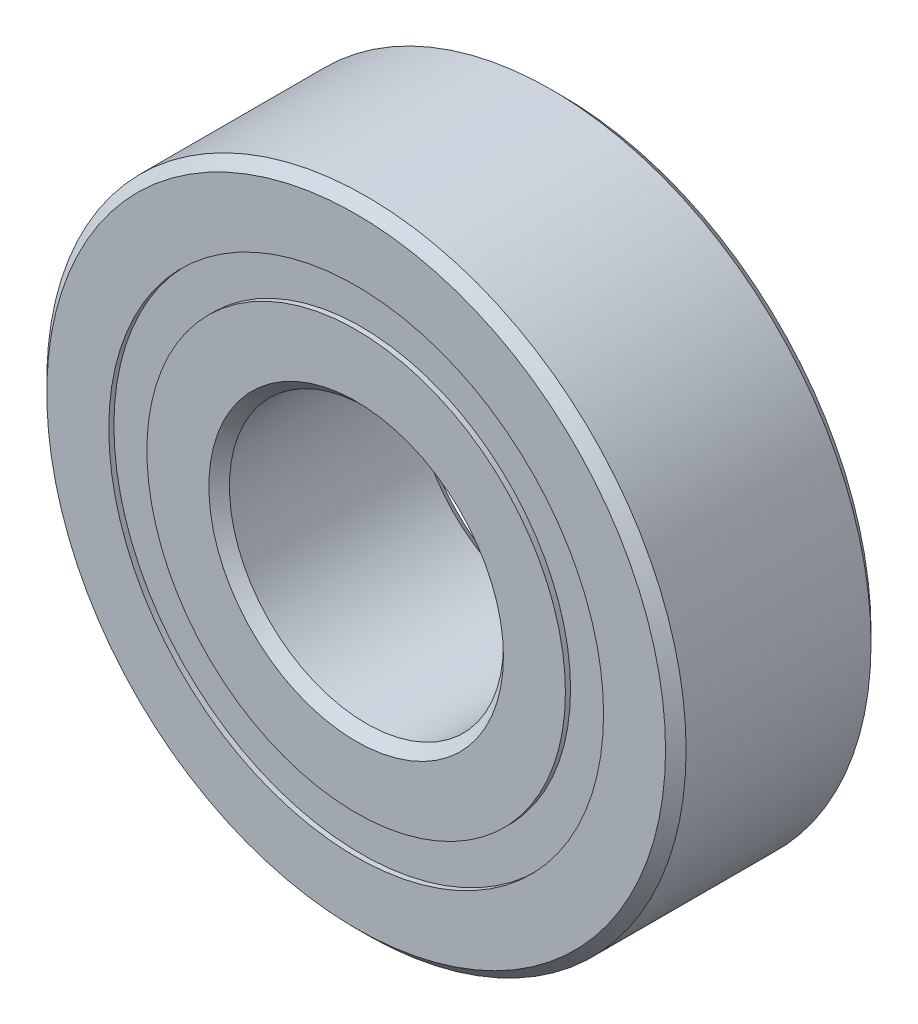
SolidWorks part; units mm, degrees
note: '?' marks a value the reader was unsure of.
ref_plane "Front Plane" through (0, 0, 0) normal (0, 0, 1) x (1, 0, 0)
ref_plane "Top Plane" through (0, 0, 0) normal (0, 1, 0) x (1, 0, 0)
ref_plane "Right Plane" through (0, 0, 0) normal (1, 0, 0) x (0, 0, -1)
sketch "Sketch1" plane through (0, 0, 0) normal (1, 0, 0) x (0, 0, -1)
  line L0 (-3.5719, 0) -> (3.5719, 0) construction
  line L1 (0, 11.1125) -> (0, -11.1125) construction
  line L2 (3.2147, 11.1125) -> (-3.2147, 11.1125)
  line L3 (-3.2147, 11.1125) -> (-3.5719, 10.7553)
  line L4 (-3.5719, 10.7553) -> (-3.5719, 8.6004)
  line L5 (-3.5719, 8.6004) -> (-1.5875, 8.6004)
  line L6 (3.5719, 8.6004) -> (1.5875, 8.6004)
  line L7 (3.5719, 10.7553) -> (3.5719, 8.6004)
  line L8 (3.2147, 11.1125) -> (3.5719, 10.7553)
  line L9 (0, 11.1125) -> (0, 7.9375) construction
  line L10 (0, 7.9375) -> (0, 4.7625) construction
  arc A0 (-1.5875, 8.6004) -> (1.5875, 8.6004) centre (0, 7.9375) cw
  point P14 (0, 4.7625)
  dimension "Width" = 7.1437
  dimension "OD" = 22.225
  dimension "D1" = 45
  dimension "D2" = 0.3572
  dimension "Shaft Dia" = 9.525
  dimension "D3" = 3.175
  dimension "D4" = 0.6629
revolve "Revolve1" add sketch "Sketch1" angle 360 about L0
sketch "Sketch3" plane through (0, 0, 0) normal (1, 0, 0) x (0, 0, -1)
  line L0 (-3.5719, 7.2746) -> (-1.5875, 7.2746)
  line L1 (0, 11.1125) -> (0, -11.1125) construction
  line L2 (-3.5719, 10.7553) -> (-3.5719, 8.6004) construction
  line L3 (-3.5719, 7.2746) -> (-3.5719, 5.1197)
  line L4 (-3.2147, 11.1125) -> (-3.5719, 10.7553) construction
  line L5 (-3.5719, 5.1197) -> (-3.2147, 4.7625)
  line L6 (-3.2147, 4.7625) -> (3.2147, 4.7625)
  line L7 (3.2147, 11.1125) -> (3.2147, -11.1125) construction
  line L8 (3.2147, 4.7625) -> (3.5719, 5.1197)
  line L9 (3.5719, -10.7553) -> (3.5719, 10.7553) construction
  line L10 (3.5719, 5.1197) -> (3.5719, 7.2746)
  line L11 (3.5719, 7.2746) -> (1.5875, 7.2746)
  line L13 (3.2147, 11.1125) -> (3.5719, 10.7553) construction
  arc A0 (1.5875, 8.6004) -> (-1.5875, 8.6004) centre (0, 7.9375) ccw construction
  arc A1 (1.5875, 7.2746) -> (-1.5875, 7.2746) centre (0, 7.9375) cw
revolve "Revolve3" add sketch "Sketch3" angle 360 about L0
sketch "Sketch4" plane through (0, 0, 0) normal (1, 0, 0) x (0, 0, -1)
  line L0 (-1.7204, 7.9375) -> (1.7204, 7.9375)
  arc A2 (-1.7204, 7.9375) -> (1.7204, 7.9375) centre (0, 7.9375) cw
  arc A3 (1.5875, 8.6004) -> (-1.5875, 8.6004) centre (0, 7.9375) ccw construction
revolve "Revolve4" add sketch "Sketch4" angle 360 about L0
ref_axis "Axis1" through (0, 0, -3.5719) along (0, 0, 1)?
pattern_circular "CirPattern1" count 10 every 36 about axis through (0, 0, 0) along (0, 0, 1) of bodies 104
sketch "Sketch5" plane through (0, 0, 0) normal (1, 0, 0) x (0, 0, -1)
  line L0 (-3.5719, 8.6004) -> (-1.5875, 8.6004) construction
  line L1 (-3.3933, 8.6004) -> (-1.7204, 8.6004)
  line L2 (-3.3933, 8.6004) -> (-3.3933, 7.2746)
  line L3 (-3.3933, 7.2746) -> (-1.7204, 7.2746)
  line L4 (-1.7204, 8.6004) -> (-1.7204, 7.2746)
  line L5 (-3.5719, 7.2746) -> (-1.5875, 7.2746) construction
  line L6 (3.5719, 8.6004) -> (1.5875, 8.6004) construction
  line L7 (3.3933, 8.6004) -> (1.7204, 8.6004)
  line L8 (3.3933, 8.6004) -> (3.3933, 7.2746)
  line L9 (3.3933, 7.2746) -> (1.7204, 7.2746)
  line L10 (1.7204, 8.6004) -> (1.7204, 7.2746)
  line L11 (3.5719, 7.2746) -> (1.5875, 7.2746) construction
  line L12 (-3.2147, 11.1125) -> (-3.5719, 10.7553) construction
  point P18 (-3.3933, 10.9339)
revolve "Revolve5" add sketch "Sketch5" angle 360 about L0
equation "\"D2@Sketch1\" = \"Width@Sketch1\"*.05"
equation "\"D3@Sketch1\" = \"Width@Sketch1\"/2.25"
equation "\"D4@Sketch1\" = (((\"OD@Sketch1\"-\"Width@Sketch1\")/2)/3.25)/3.5"
equation "\"D2@CirPattern1\" = 360/\"Balls@CirPattern1\""
